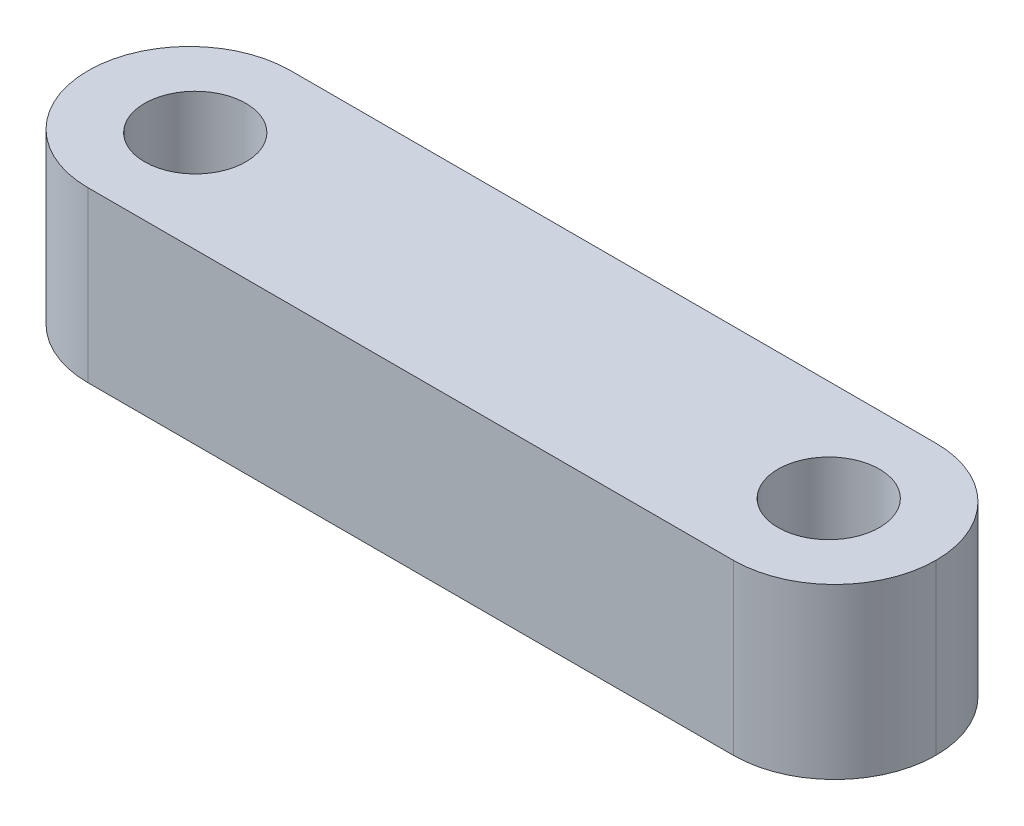
SolidWorks part; units mm, degrees
ref_plane "Front Plane" through (0, 0, 0) normal (0, 0, 1) x (1, 0, 0)
ref_plane "Top Plane" through (0, 0, 0) normal (0, 1, 0) x (1, 0, 0)
ref_plane "Right Plane" through (0, 0, 0) normal (1, 0, 0) x (0, 0, -1)
sketch "Sketch1" plane through (0, 0, 0) normal (0, 1, 0) x (1, 0, 0)
  line L0 (-18.75, 0) -> (18.75, 0) construction
  line L2 (-25.1, -6) -> (25.1, -6)
  line L3 (-25.1, -6) -> (-25.1, 6)
  line L4 (-25.1, 6) -> (25.1, 6)
  line L5 (25.1, -6) -> (25.1, 6)
  line L6 (-25.1, -6) -> (25.1, 6) construction
  line L7 (-25.1, 6) -> (25.1, -6) construction
  circle A0 centre (18.75, 0) radius 3
  circle A1 centre (-18.75, 0) radius 3
  point P4 (0, 0)
  point P7 (0, 0)
  dimension "D2" = 6
  dimension "D3" = 6
  dimension "D1" = 37.5
  dimension "D4" = 12
  dimension "D5" = 6.35
extrude "Boss-Extrude1" add sketch "Sketch1" along normal blind 10 contours A1 | A0 | L4 L5 L2 L3 region at (18.75, 0, 0) region at (-18.75, 0, 0)
fillet "Fillet1" radius 6 4 edges at (25.1, 5, -6) (25.1, 5, 6) (-25.1, 5, -6) (-25.1, 5, 6)
